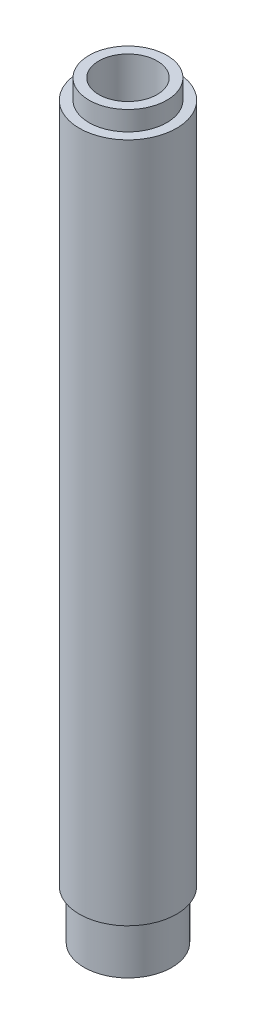
SolidWorks part; units mm, degrees
ref_plane "Front Plane" through (0, 0, 0) normal (0, 0, 1) x (1, 0, 0)
ref_plane "Top Plane" through (0, 0, 0) normal (0, 1, 0) x (1, 0, 0)
ref_plane "Right Plane" through (0, 0, 0) normal (1, 0, 0) x (0, 0, -1)
sketch "Sketch1" plane through (0, 0, 0) normal (0, 1, 0) x (1, 0, 0)
  circle A0 centre (0, 0) radius 12.7
  dimension "D1" = 25.4
extrude "Boss-Extrude1" add sketch "Sketch1" along normal blind 177.8
sketch "Sketch4" plane through (0, 177.8, 0) normal (0, 1, 0) x (1, 0, 0)
  circle A2 centre (0, 0) radius 10.16
  circle A3 centre (0, 0) radius 10.16
  dimension "D1" = 2.54
extrude "Boss-Extrude2" add sketch "Sketch4" along normal blind 5.08
sketch "Sketch5" plane through (0, 182.88, 0) normal (0, 1, 0) x (1, 0, 0)
  circle A0 centre (0, 0) radius 10.16 construction
  circle A1 centre (0, 0) radius 10.16 construction
  circle A2 centre (0, 0) radius 7.62
  dimension "D1" = 2.54
extrude "Cut-Extrude1" cut sketch "Sketch5" against normal through all
sketch "Sketch6" plane through (0, 0, 0) normal (0, -1, 0) x (1, 0, 0)
  circle A0 centre (0, 0) radius 11.43
  circle A1 centre (0, 0) radius 7.62 construction
  circle A2 centre (0, 0) radius 7.62
  dimension "D1" = 22.86
extrude "Boss-Extrude3" add sketch "Sketch6" along normal blind 12.7
sketch "Sketch7" plane through (0, -12.7, 0) normal (0, -1, 0) x (1, 0, 0)
  circle A0 centre (0, 0) radius 12.7 construction
  circle A1 centre (0, 0) radius 12.7
sketch "Sketch8" plane through (0, 182.88, 0) normal (0, 1, 0) x (1, 0, 0)
  circle A0 centre (0, 0) radius 12.7 construction
  circle A1 centre (0, 0) radius 12.7
